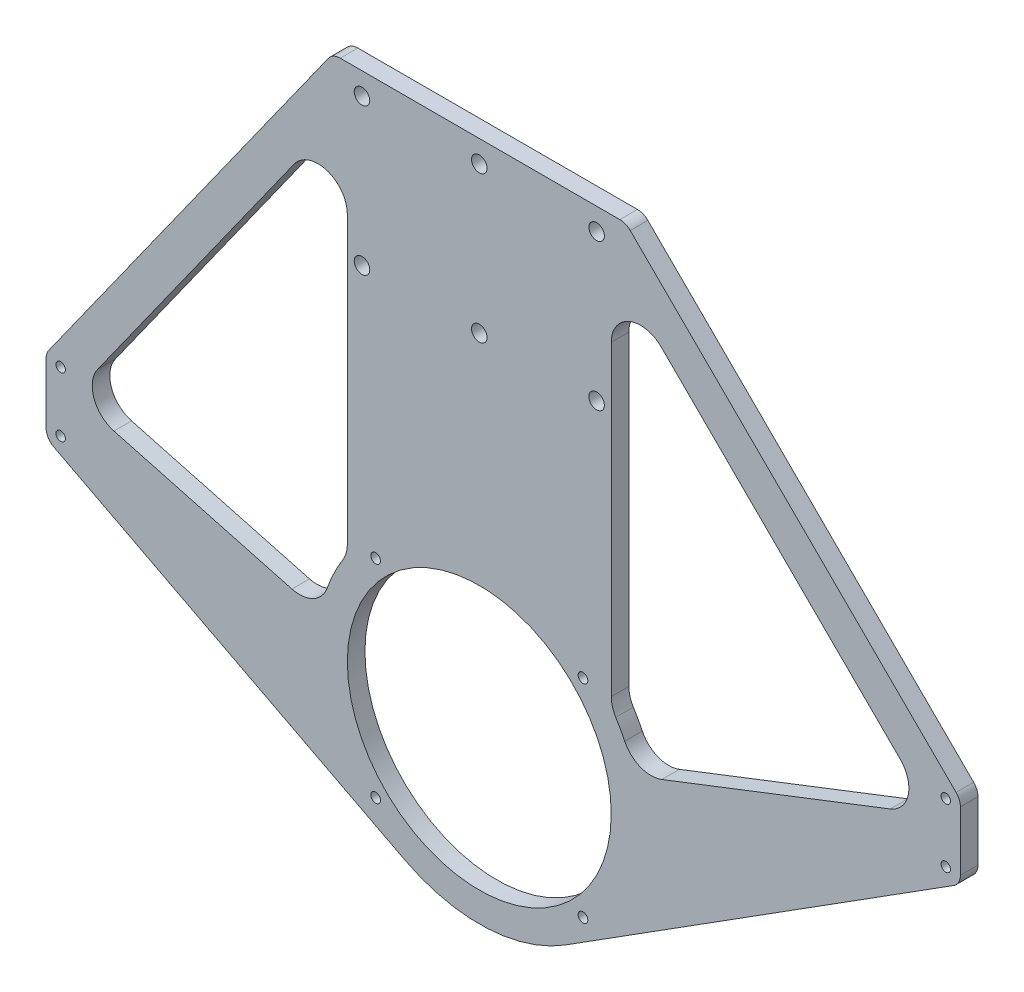
SolidWorks part; units mm, degrees
ref_plane "Front" through (0, 0, 0) normal (0, 0, 1) x (1, 0, 0)
ref_plane "Top" through (0, 0, 0) normal (0, 1, 0) x (1, 0, 0)
ref_plane "Right" through (0, 0, 0) normal (1, 0, 0) x (0, 0, -1)
sketch "Body Driving Dimensions" plane through (0, 0, 0) normal (0, 0, 1) x (1, 0, 0)
  line L0 (0, 0) -> (45.3825, -53.2956)
  line L1 (45.3825, -53.2956) -> (0, -248.0787)
  line L2 (0, -248.0787) -> (-45.3825, -53.2956)
  line L3 (-45.3825, -53.2956) -> (0, 0)
  line L4 (0, 0) -> (0, -36.971) construction
  line L5 (0, 0) -> (149.1516, 57.912)
  line L6 (149.1516, 57.912) -> (45.3825, -53.2956)
  line L7 (0, 0) -> (-132.3071, 35.5506)
  line L8 (-132.3071, 35.5506) -> (-45.3825, -53.2956)
  line L9 (149.1516, 57.912) -> (242.3794, 94.1101) construction
  line L10 (-132.3071, 35.5506) -> (-228.8899, 61.5022) construction
  line L11 (149.1516, 57.912) -> (149.1516, 26.2399) construction
  line L12 (-132.3071, 35.5506) -> (-132.3071, 3.8785) construction
  line L13 (0, 0) -> (-98.8336, -98.8336) construction
  line L14 (0, 0) -> (98.8336, -98.8336) construction
  dimension "D1" = 45
  dimension "D2" = 45
  dimension "D3" = 200
  dimension "D4" = 70
  dimension "D5" = 160
  dimension "D6" = 137
  dimension "D7" = 111.22
  dimension "D8" = 105.04
sketch "Sketch1" plane through (0, 0, 0) normal (0, 0, 1) x (1, 0, 0)
  line L0 (-45.3825, -53.2956) -> (0, -248.0787) construction
  line L1 (-38.0782, -51.5938) -> (7.3044, -246.3768)
  line L2 (-52.6869, -54.9975) -> (-7.3044, -249.7805)
  circle A0 centre (-45.3825, -53.2956) radius 3.5
  circle A1 centre (0, -248.0787) radius 3.5
  arc A2 (-38.0782, -51.5938) -> (-52.6869, -54.9975) centre (-45.3825, -53.2956) ccw
  arc A3 (-7.3044, -249.7805) -> (7.3044, -246.3768) centre (0, -248.0787) ccw
  point P6 (-22.6913, -150.6871)
  dimension "D1" = 7
  dimension "D2" = 7.5
extrude "Tibya" [suppressed] add sketch "Sketch1" along normal blind 6
sketch "Sketch2" [suppressed] plane through (0, 0, 0) normal (0, 0, 1) x (1, 0, 0)
  line L0 (0, 0) -> (70, 0) construction
  line L1 (0, 0) -> (45.3825, -53.2956) construction
  line L2 (70.6537, 7.4715) -> (17.125, 12.1546)
  line L4 (70.6537, -7.4715) -> (17.125, -12.1546)
  circle A0 centre (0, 0) radius 17.5 construction
  circle A1 centre (0, 17.5) radius 1.65
  circle A2 centre (-17.5, 0) radius 1.65
  circle A3 centre (17.5, 0) radius 1.65
  circle A4 centre (0, -17.5) radius 1.65
  circle A5 centre (70, 0) radius 3.5
  circle A6 centre (70, 0) radius 7.5 construction
  circle A7 centre (0, 0) radius 21 construction
  arc A8 (70.6537, 7.4715) -> (70.6537, -7.4715) centre (70, 0) cw
  arc A9 (17.125, 12.1546) -> (17.125, -12.1546) centre (0, 0) ccw
  circle A10 centre (0, 0) radius 7
  dimension "D1" = 3.3
  dimension "D2" = 35
  dimension "D3" = 7
  dimension "D4" = 42
  dimension "D5" = 15
  dimension "D6" = 14
  dimension "D7" = 5
extrude "Boss-Extrude2" [suppressed] add sketch "Sketch2" along normal blind 6
fillet "Fillet1" [suppressed] radius 5
sketch "Sketch4" [suppressed] plane through (0, 0, 0) normal (1, 0, 0) x (0, 0, -1)
  line L0 (27.75, 0) -> (-27.75, 0)
  point P4 (0, 0)
  dimension "D1" = 55.5
sketch "Sketch5" [suppressed] plane through (0, 0, 0) normal (0, 1, 0) x (1, 0, 0)
  circle A0 centre (0, 0) radius 3.5
  circle A2 centre (0, 0) radius 3.25
  dimension "D1" = 7
  dimension "D2" = 0.25
extrude "Boss-Extrude3" [suppressed] add sketch "Sketch5" against normal blind 278
sketch "Sketch6" plane through (0, 0, 0) normal (0, 0, 1) x (1, 0, 0)
  line L0 (-18.9268, 67.3927) -> (-132.3071, 35.5506) construction
  line L1 (5.7655, 69.7622) -> (149.1516, 57.912) construction
  circle A0 centre (0, 0) radius 70 construction
  circle A1 centre (0, 0) radius 160 construction
  circle A2 centre (0, 0) radius 137 construction
sketch "Sketch8" plane through (0, 0, 0) normal (0, 0, 1) x (1, 0, 0)
  line L0 (0, 0) -> (0, 177) construction
  line L1 (50, 177) -> (-50, 177)
  line L2 (-50, 177) -> (-147.759, 39.7025)
  line L3 (0, 177) -> (0, 137) construction
  line L4 (-132.3071, 35.5506) -> (-228.8899, 61.5022) construction
  line L5 (-147.759, 39.7025) -> (-147.759, 14.7025)
  line L6 (-147.759, 14.7025) -> (-25.3303, -48.8199)
  line L7 (0, 0) -> (-132.3071, 35.5506) construction
  line L8 (149.1516, 57.912) -> (242.3794, 94.1101) construction
  line L9 (50, 177) -> (164.0668, 63.7032)
  line L10 (164.0668, 63.7032) -> (164.0668, 38.7032)
  line L11 (164.0668, 38.7032) -> (29.4025, -46.4811)
  line L12 (40, 169.5) -> (-40, 169.5) construction
  line L13 (40, 119.5) -> (-40, 119.5) construction
  circle A0 centre (0, 0) radius 55 construction
  circle A1 centre (0, 0) radius 160 construction
  circle A2 centre (0, 0) radius 45
  arc A3 (-25.3303, -48.8199) -> (29.4025, -46.4811) centre (0, 0) ccw
  circle A4 centre (-40, 169.5) radius 2.65
  circle A5 centre (0, 0) radius 137 construction
  circle A6 centre (40, 169.5) radius 2.65
  circle A7 centre (0, 169.5) radius 2.65
  circle A8 centre (40, 119.5) radius 2.65
  circle A9 centre (0, 119.5) radius 2.65
  circle A10 centre (-40, 119.5) radius 2.65
  point P12 (0, 160)
  point P26 (0, 169.5)
  point P37 (0, 119.5)
  dimension "D2" = 110
  dimension "D3" = 90
  dimension "D10" = 5.3
  dimension "D4" = 16
  dimension "D5" = 16
  dimension "D6" = 25
  dimension "D1" = 100
  dimension "D8" = 10
  dimension "D9" = 7.5
  dimension "D11" = 80
  dimension "D12" = 50
  dimension "D7" = 177
  dimension "D13" = 40
extrude "Boss-Extrude4" add sketch "Sketch8" along normal blind 6
sketch "Sketch9" plane through (0, 0, 0) normal (0, 0, -1) x (-1, 0, 0)
  line L0 (0, 0) -> (35.3553, -35.3553) construction
  line L1 (0, 0) -> (0, -36.971) construction
  circle A0 centre (0, 0) radius 50 construction
  circle A1 centre (35.3553, -35.3553) radius 1.65
  circle A2 centre (-35.3553, -35.3553) radius 1.65
  circle A3 centre (-35.3553, 35.3553) radius 1.65
  circle A4 centre (35.3553, 35.3553) radius 1.65
  point P16 (0, 0)
  dimension "D1" = 100
  dimension "D3" = 3.3
  dimension "D2" = 45
  dimension "D4" = 4
extrude "Cut-Extrude1" cut sketch "Sketch9" against normal through all
sketch "Sketch10" plane through (0, 0, 0) normal (0, 0, -1) x (-1, 0, 0)
  line L0 (45, 31.6228) -> (45, 163.3332)
  line L1 (45, 163.3332) -> (138.488, 32.034)
  line L2 (138.488, 32.034) -> (54.1935, 9.3843)
  line L3 (0, 55) -> (0, 163.3332) construction
  line L4 (50, 177) -> (147.759, 39.7025) construction
  line L5 (132.3071, 35.5506) -> (228.8899, 61.5022) construction
  line L6 (-52.8683, 15.1638) -> (-154.4619, 54.6102)
  line L7 (-154.4619, 54.6102) -> (-45, 163.3332)
  line L8 (-45, 163.3332) -> (-45, 31.6228)
  line L9 (-149.1516, 57.912) -> (-242.3794, 94.1101) construction
  line L10 (-164.0668, 63.7032) -> (-50, 177) construction
  line L11 (-45, 163.3332) -> (45, 163.3332) construction
  line L12 (0, 55) -> (0, 0) construction
  circle A0 centre (0, 0) radius 55 construction
  arc A1 (54.1935, 9.3843) -> (45, 31.6228) centre (0, 0) ccw
  arc A2 (-45, 31.6228) -> (-52.8683, 15.1638) centre (0, 0) ccw
  point P19 (0, 163.3332)
  dimension "D1" = 110
  dimension "D4" = 5
  dimension "D5" = 5
  dimension "D3" = 12
  dimension "D2" = 90
  dimension "D6" = 13.2201
extrude "Cut-Extrude2" cut sketch "Sketch10" against normal through all
fillet "Fillet2" radius 10 8 edges at (-54.1935, 9.3843, 3) (-45, 31.6228, 3) (52.8683, 15.1638, 3) (45, 31.6228, 3) (154.4619, 54.6102, 3) (-138.488, 32.034, 3) (45, 163.3332, 3) (-45, 163.3332, 3)
fillet "Fillet3" radius 5 6 edges at (164.0668, 38.7032, 3) (164.0668, 63.7032, 3) (-147.759, 14.7025, 3) (-147.759, 39.7025, 3) (50, 177, 3) (-50, 177, 3)
sketch "Sketch11" plane through (0, 0, 0) normal (0, 0, -1) x (-1, 0, 0)
  circle A0 centre (142.759, 38.1043) radius 1.6
  circle A1 centre (142.759, 17.7412) radius 1.6
  circle A2 centre (-159.0668, 61.6222) radius 1.6
  circle A3 centre (-159.0668, 41.4567) radius 1.6
  dimension "D1" = 3.2
  dimension "D2" = 20.3631
extrude "Cut-Extrude3" cut sketch "Sketch11" against normal through all
sketch "Sketch12" [suppressed] plane through (0, 0, 0) normal (0, 0, -1) x (-1, 0, 0)
  line L0 (214.1882, 56.4553) -> (214.1882, 37.1954) construction
  line L1 (219.1882, 56.4553) -> (219.1882, 37.1954)
  line L2 (209.1882, 56.4553) -> (209.1882, 37.1954)
  line L4 (203.7362, 54.7434) -> (228.8899, 61.5022) construction
  arc A0 (219.1882, 56.4553) -> (209.1882, 56.4553) centre (214.1882, 56.4553) ccw
  arc A1 (209.1882, 37.1954) -> (219.1882, 37.1954) centre (214.1882, 37.1954) ccw
  arc A2 (219.1882, 56.4553) -> (217.2648, 60.3967) centre (214.1882, 56.4553) ccw construction
  circle A3 centre (203.7362, 54.7434) radius 2.5
  circle A4 centre (203.7362, 54.7434) radius 6.5
  circle A5 centre (214.1882, 56.4553) radius 2.55
  circle A6 centre (203.7362, 54.7434) radius 4.5 construction
  point P4 (214.1882, 46.8254)
  dimension "D2" = 5
  dimension "D3" = 13
  dimension "D4" = 5.1
  dimension "D5" = 9
sketch "Sketch13" [suppressed] plane through (0, 0, 0) normal (0, 0, -1) x (-1, 0, 0)
  line L0 (209.1882, 56.4553) -> (209.1882, 37.1954) construction
  line L1 (219.1882, 56.4553) -> (219.1882, 37.1954) construction
  line L2 (209.1882, 56.4553) -> (209.1882, 37.1954)
  line L3 (219.1882, 56.4553) -> (219.1882, 37.1954)
  arc A0 (219.1882, 56.4553) -> (209.1882, 56.4553) centre (214.1882, 56.4553) ccw construction
  arc A1 (219.1882, 56.4553) -> (209.1882, 56.4553) centre (214.1882, 56.4553) ccw
  arc A2 (209.1882, 37.1954) -> (219.1882, 37.1954) centre (214.1882, 37.1954) ccw construction
  arc A3 (209.1882, 37.1954) -> (219.1882, 37.1954) centre (214.1882, 37.1954) ccw
extrude "Boss-Extrude5" [suppressed] add sketch "Sketch13" along normal blind 80.5 separate body
delete or keep bodies "Body-Delete/Keep 1" [suppressed] type delete bodies bodies 107
sketch "Sketch14" [suppressed] plane through (0, 0, -80.5) normal (0, 0, -1) x (-1, 0, 0)
  circle A0 centre (214.1882, 56.4553) radius 2.85
  circle A1 centre (214.1882, 37.1954) radius 2.85
  dimension "D1" = 5.7
extrude "Cut-Extrude4" [suppressed] cut sketch "Sketch14" against normal blind 8
ref_plane "Plane1" [suppressed] through (0, 0, -40.25) normal (0, 0, -1) x (-1, 0, 0)
mirror "Mirror1" [suppressed] about plane through (0, 0, -40.25) normal (0, 0, -1)
ref_plane "Plane2" [suppressed] through (0, 0, -31.9) normal (0, 0, 1) x (1, 0, 0)
sketch "Sketch15" [suppressed] plane through (0, 0, -31.9) normal (0, 0, 1) x (1, 0, 0)
  line L3 (-210.2362, 54.7434) -> (-203.7362, 54.7434) construction
  line L5 (-203.6047, 61.2421) -> (-214.087, 61.4543)
  line L6 (-203.6047, 48.2448) -> (-209.1882, 48.1317)
  line L7 (-209.1882, 56.4553) -> (-209.1882, 37.1954) construction
  line L8 (-209.1882, 48.1317) -> (-214.087, 61.4543)
  circle A0 centre (-203.7362, 54.7434) radius 6.5 construction
  arc A2 (-203.6047, 61.2421) -> (-203.6047, 48.2448) centre (-203.7362, 54.7434) cw
  circle A3 centre (-203.7362, 54.7434) radius 4
  arc A4 (-209.1882, 56.4553) -> (-219.1882, 56.4553) centre (-214.1882, 56.4553) ccw construction
  dimension "D3" = 8
  dimension "D1" = 1.16
  dimension "D2" = 1.16
extrude "Boss-Extrude6" [suppressed] add sketch "Sketch15" along normal blind 5.5 and the other way blind 5.5
sketch "Sketch16" [suppressed] plane through (0, 0, -31.9) normal (0, 0, 1) x (1, 0, 0)
  circle A0 centre (-203.7362, 54.7434) radius 6.5
  circle A1 centre (-203.7362, 54.7434) radius 6.5 construction
extrude "Cut-Extrude5" [suppressed] cut sketch "Sketch16" against normal blind 1 and the other way blind 1
fillet "Fillet5" [suppressed] radius 5
chamfer "Chamfer1" [suppressed] distance 0.5 angle 70
sketch "Sketch17" [suppressed] plane through (0, 0, 0) normal (0, 0, 1) x (1, 0, 0)
  line L0 (0, 0) -> (-45, 0) construction
  line L1 (0, 0) -> (0, 45) construction
  line L2 (0, 0) -> (-35.3553, 35.3553) construction
  line L3 (0, 0) -> (0, 170) construction
  line L4 (54, 170) -> (-54, 170)
  line L5 (-54, 170) -> (-54, 0)
  line L6 (54, 0) -> (54, 170)
  line L7 (45, 162.5) -> (-45, 162.5) construction
  line L8 (45, 112.5) -> (-45, 112.5) construction
  circle A0 centre (0, 0) radius 45
  circle A1 centre (-35.3553, 35.3553) radius 1.65
  circle A2 centre (35.3553, 35.3553) radius 1.65
  circle A3 centre (35.3553, -35.3553) radius 1.65
  circle A4 centre (-35.3553, -35.3553) radius 1.65
  circle A5 centre (0, 0) radius 54 construction
  circle A6 centre (0, 162.5) radius 2.65
  arc A7 (-54, 0) -> (54, 0) centre (0, 0) ccw
  circle A8 centre (-45, 162.5) radius 2.65
  circle A9 centre (45, 162.5) radius 2.65
  circle A10 centre (-45, 112.5) radius 2.65
  circle A11 centre (-35.3553, 35.3553) radius 4 construction
  circle A12 centre (0, 112.5) radius 2.65
  circle A13 centre (45, 112.5) radius 2.65
  point P16 (0, 0)
  point P19 (0, 170)
  point P25 (0, 162.5)
  point P33 (0, 112.5)
  dimension "D1" = 90
  dimension "D4" = 3.3
  dimension "D6" = 170
  dimension "D9" = 5.3
  dimension "D11" = 8
  dimension "D7" = 50
  dimension "D2" = 45
  dimension "D3" = 50
  dimension "D8" = 90
  dimension "D10" = 7.5
  dimension "D5" = 4
extrude "Simple Side Plate" [suppressed] add sketch "Sketch17" along normal blind 6
fillet "Fillet7" [suppressed] radius 2.5
equation "\"l2\"= 200"
equation "\"D3@Body Driving Dimensions\" = \"l2\""
equation "\"l1\"= 70"
equation "\"D4@Body Driving Dimensions\" = \"l1\""
equation "\"s1r\"= 1.94122348320248rad"
equation "\"s2r\"= - 1.833281132rad"
equation "\"offset\"= 10mm"
equation "\"s1_len\"= 0.08m"
equation "\"s2_len\"= 0.127m"
equation "\"s1_anchor_dist\"= \"offset\" + \"l1\" + \"s1_len\""
equation "\"s2_anchor_dist\"= \"offset\" + \"s2_len\"'this was: = \"offset\" + \"l1\" + \"s2_len\""
equation "\"D5@Body Driving Dimensions\" = \"s1_anchor_dist\""
equation "\"D6@Body Driving Dimensions\" = \"s2_anchor_dist\""
equation "\"D7@Body Driving Dimensions\" = \"s1r\""
equation "\"D8@Body Driving Dimensions\" =  - \"s2r\""
equation "\"carbon_fiber_plate_thickness\"=6"
equation "\"D1@Tibya\" = \"carbon_fiber_plate_thickness\""
equation "\"D1@Boss-Extrude2\"=\"carbon_fiber_plate_thickness\""
equation "\"motor_to_motor_spacing\"=55.5"
equation "\"D1@Sketch4\"=\"motor_to_motor_spacing\""
equation "\"D1@Boss-Extrude3\"=\"l1\"+\"l2\" + 8"
equation "\"D5@Sketch8\"=\"D4@Sketch8\""
equation "\"D5@Sketch10\"=\"D4@Sketch10\""
equation "\"D2@Sketch15\"=\"D1@Sketch15\""
equation "\"D7@Sketch8\"=\"l2\" - \"l1\" + 47"
